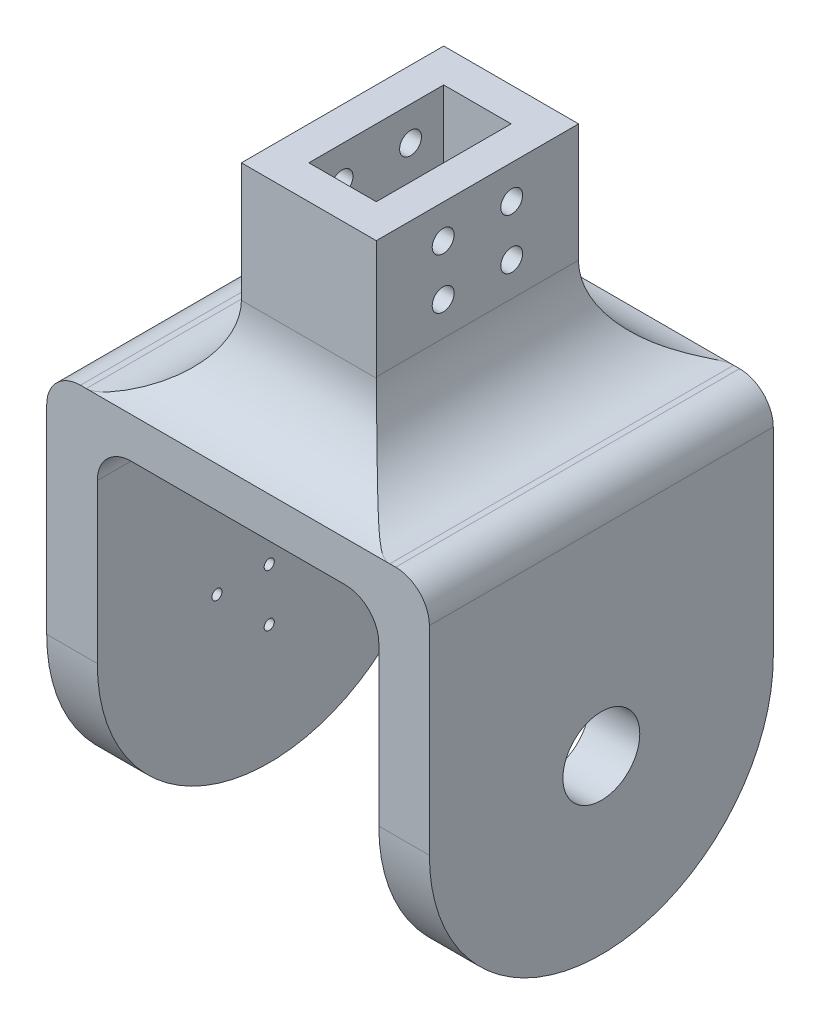
SolidWorks part; units mm, degrees
ref_plane "Alzado" through (0, 0, 0) normal (0, 0, 1) x (1, 0, 0)
ref_plane "Planta" through (0, 0, 0) normal (0, 1, 0) x (1, 0, 0)
ref_plane "Vista lateral" through (0, 0, 0) normal (1, 0, 0) x (0, 0, -1)
sketch "Croquis1" plane through (0, 0, 0) normal (0, 0, 1) x (1, 0, 0)
  line L0 (0, 0) -> (0, 46.6425) construction
  line L2 (-41.75, 0) -> (-56.75, 0)
  line L3 (-41.75, 0) -> (-41.75, 98)
  line L5 (-56.75, 0) -> (-56.75, 110)
  line L6 (-31.75, 108) -> (31.75, 108)
  line L8 (-46.75, 120) -> (46.75, 120)
  line L12 (0, 108) -> (-31.75, 108)
  line L15 (56.75, 0) -> (56.75, 110)
  line L16 (41.75, 0) -> (41.75, 98)
  line L17 (41.75, 0) -> (56.75, 0)
  arc A0 (-46.75, 120) -> (-56.75, 110) centre (-46.75, 110) ccw
  arc A1 (-41.75, 98) -> (-31.75, 108) centre (-31.75, 98) cw
  arc A2 (41.75, 98) -> (31.75, 108) centre (31.75, 98) ccw
  arc A3 (46.75, 120) -> (56.75, 110) centre (46.75, 110) cw
  point P5 (0, 106.1603)
  point P8 (0, 157.6277)
  point P11 (41.0351, 149.5158)
  point P12 (0, 45.1676)
  point P13 (0, 46.6425)
  point P15 (0, 0)
  point P21 (0, 0)
  point P23 (0, 208)
  dimension "D5" = 10
  dimension "D6" = 120
  dimension "D1" = 108
  dimension "D2" = 41.75
  dimension "D3" = 15
extrude "Saliente-Extruir1" add sketch "Croquis1" along normal blind 102 contours A3 L8 A0 L5 L2 L3 A1 L6 A2 L16 L17 L15 region at (-49.25, 1.6517, 0)
sketch "Croquis2" plane through (-56.75, 0, 0) normal (-1, 0, 0) x (0, 0, 1)
  line L1 (102, 0) -> (0, 0) construction
  line L2 (0, 51) -> (102, 51)
  arc A0 (0, 51) -> (102, 51) centre (51, 51) ccw
  point P4 (51, 0)
  line M1 (0, 110) -> (0, 0)
  line M2 (0, 0) -> (102, 0)
  line M3 (102, 0) -> (102, 110)
  dimension "D1" = 102
extrude "Cortar-Extruir1" cut sketch "Croquis2" against normal through all contours A0 M1 M2 | A0 M2 M3 region at (-56.75, 11.3918, 11.3918) region at (-56.75, 11.3918, 90.6082)
sketch "Croquis3" plane through (-56.75, 0, 0) normal (-1, 0, 0) x (0, 0, 1)
  circle A0 centre (51, 51) radius 1.5
  circle A1 centre (51, 66.5) radius 1.5
  circle A2 centre (51, 66.5) radius 3
  circle A3 centre (66.5, 51) radius 3
  circle A4 centre (66.5, 51) radius 1.5
  circle A5 centre (51, 35.5) radius 3
  circle A6 centre (51, 35.5) radius 1.5
  circle A7 centre (35.5, 51) radius 3
  circle A8 centre (35.5, 51) radius 1.5
  dimension "D1" = 3
  dimension "D2" = 6
  dimension "D3" = 3
  dimension "D4" = 15.5
  dimension "D5" = 4
extrude "Cortar-Extruir2" cut sketch "Croquis3" against normal blind 30 contours A8 | A1 | A4 | A0 | A6 region at (-56.75, 51, 51) region at (-56.75, 66.5, 51) region at (-56.75, 51, 66.5) region at (-56.75, 35.5, 51) region at (-56.75, 51, 35.5)
extrude "Cortar-Extruir3" cut sketch "Croquis3<3>" against normal blind 5 contours A7 A8 | A2 A1 | A3 A4 | A5 A6 region at (-56.75, 66.5, 48.0849) region at (-56.75, 51, 63.5849) region at (-56.75, 35.5, 48.0849) region at (-56.75, 51, 32.5849)
sketch "Croquis3<3>" plane through (-56.75, 0, 0) normal (-1, 0, 0) x (0, 0, 1) same geometry as "Croquis3"
chamfer "Chaflán1" distance 0.4 angle 45 4 edges at (-56.75, 35.5, 54) (-56.75, 51, 69.5) (-56.75, 66.5, 54) (-56.75, 51, 38.5)
sketch "Croquis5" plane through (56.75, 0, 0) normal (1, 0, 0) x (0, 0, -1)
  circle A1 centre (-51, 51) radius 11.4
  dimension "D1" = 22.8
extrude "Cortar-Extruir4" cut sketch "Croquis5" against normal blind 30
sketch "Croquis6" plane through (0, 120, 0) normal (0, 1, 0) x (1, 0, 0)
  line L1 (-10, -31) -> (10, -31)
  line L2 (-10, -31) -> (-10, -71)
  line L3 (-10, -71) -> (10, -71)
  line L4 (10, -31) -> (10, -71)
  line L5 (-10, -31) -> (10, -71) construction
  line L6 (-10, -71) -> (10, -31) construction
  line L10 (-46.75, -102) -> (46.75, -102) construction
  line L11 (-20, -21) -> (20, -21)
  line L12 (20, -21) -> (20, -81)
  line L13 (-20, -81) -> (20, -81)
  line L14 (-20, -21) -> (-20, -81)
  point P0 (0, -51)
  point P5 (5.8073, -54.949)
  point P8 (0, -51.542)
  dimension "D1" = 51
  dimension "D2" = 40
  dimension "D3" = 20
  dimension "D4" = 10
extrude "Saliente-Extruir2" add sketch "Croquis6" along normal blind 60
fillet "Redondeo2" radius 25 4 edges at (0, 120, 21) (-20, 120, 51) (0, 120, 81) (20, 120, 51)
sketch "Croquis7" plane through (-20, 0, 0) normal (-1, 0, 0) x (0, 0, 1)
  line L0 (21, 180) -> (21, 145) construction
  line L1 (21, 180) -> (81, 180) construction
  line L2 (51, 180) -> (51, 146.5068) construction
  line L3 (21, 162.5) -> (76.7585, 162.5) construction
  circle A0 centre (40.8348, 170) radius 3.25
  circle A1 centre (61.1652, 170) radius 3.25
  circle A2 centre (61.1652, 155) radius 3.25
  circle A3 centre (40.8348, 155) radius 3.25
  dimension "D2" = 6.5
  dimension "D1" = 19.8348
  dimension "D3" = 10
extrude "Cortar-Extruir5" cut sketch "Croquis7" against normal through all
